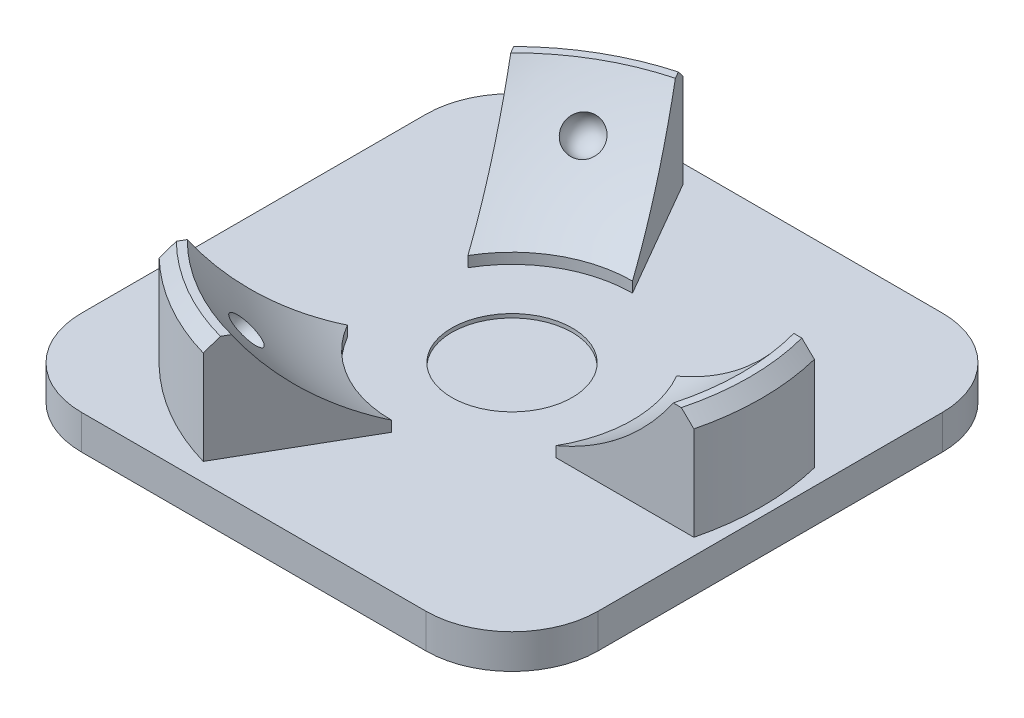
SolidWorks part; units mm, degrees
ref_plane "Спереди" through (0, 0, 0) normal (0, 0, 1) x (1, 0, 0)
ref_plane "Сверху" through (0, 0, 0) normal (0, 1, 0) x (1, 0, 0)
ref_plane "Справа" through (0, 0, 0) normal (1, 0, 0) x (0, 0, -1)
other "Configuration Table"
sketch "Эскиз1" plane through (0, 0, 0) normal (0, 0, 1) x (1, 0, 0)
  line L0 (11.1355, 0) -> (28.9914, 0)
  line L1 (28.9914, 0) -> (28.9914, 10.9081)
  line L2 (28.9914, 10.9081) -> (27.5772, 12.3223)
  line L3 (27.5772, 12.3223) -> (26.674, 12.3223)
  line L5 (0, 30) -> (44.5124, -14.5124) construction
  line L6 (17.6777, 2.4228) -> (27.5772, 12.3223) construction
  line L7 (0, 0) -> (0, 20.2249) construction
  circle A0 centre (0, 30) radius 30 construction
  circle A2 centre (22.6274, 7.3726) radius 2 construction
  circle A3 centre (0, 30) radius 32 construction
  arc A4 (26.674, 12.3223) -> (11.1355, 0) centre (0, 30) cw
  point P15 (22.6274, 7.3726)
  dimension "D1" = 60
  dimension "D2" = 4
  dimension "D7" = 64
  dimension "D3" = 14
  dimension "D4" = 135
  dimension "D5" = 2
  dimension "D6" = 45
revolve "Повернуть1" add sketch "Эскиз1" angle 360 about L7
sketch "Эскиз2" plane through (0, 0, 0) normal (0, -1, 0) x (1, 0, 0)
  line L0 (-37.3718, 0) -> (42.3587, 0) construction
  line L1 (-37.3718, -7) -> (42.3587, -7) construction
  line L2 (-37.3718, 7) -> (42.3587, 7) construction
  line L3 (4.0414, 7) -> (4.0414, -7)
  line L4 (4.0414, -7) -> (34.1437, -7)
  line L9 (28.1336, 7) -> (4.0414, 7)
  line L18 (34.1437, 7) -> (28.1336, 7)
  circle A0 centre (0, 0) radius 28.9914 construction
  arc A2 (34.1437, 7) -> (34.1437, -7) centre (0, 0) ccw
  point P22 (0, 0)
  dimension "D1" = 7
  dimension "D2" = 7
extrude "Вырез-Вытянуть1" cut sketch "Эскиз2" against normal through all
ref_axis "Ось1" through (0, 0, 0) along (0, 1, 0)
sketch "Эскиз3" plane through (0, 0, 0) normal (0, 0, 1) x (1, 0, 0)
  line L0 (0, 30) -> (43.0518, -13.0518) construction
  line L1 (0, 0) -> (0, 30) construction
  line L2 (21.2132, 8.7868) -> (24.0416, 5.9584)
  circle A0 centre (0, 30) radius 30 construction
  circle A1 centre (22.6274, 7.3726) radius 2 construction
  arc A2 (24.0416, 5.9584) -> (21.2132, 8.7868) centre (22.6274, 7.3726) cw
  dimension "D1" = 60
  dimension "D2" = 4
  dimension "D3" = 30
  dimension "D4" = 45
revolve "Вырез-Повернуть3" cut sketch "Эскиз3" angle 360 about L0
pattern_circular "Круговой массив5" count 3 over 360 about axis through (0, 0, 0) along (0, 1, 0) of "Повернуть1"
sketch "Эскиз4" plane through (0, 0, 0) normal (0, -1, 0) x (1, 0, 0)
  line L1 (-20, -30) -> (20, -30)
  line L2 (-30, -20) -> (-30, 20)
  line L3 (-20, 30) -> (20, 30)
  line L4 (30, -20) -> (30, 20)
  line L5 (-30, -30) -> (30, 30) construction
  line L6 (-30, 30) -> (30, -30) construction
  arc A0 (-30, 20) -> (-20, 30) centre (-20, 20) cw
  arc A1 (-20, -30) -> (-30, -20) centre (-20, -20) cw
  arc A2 (20, -30) -> (30, -20) centre (20, -20) ccw
  arc A3 (20, 30) -> (30, 20) centre (20, 20) cw
  point P0 (0, 0)
  dimension "D3" = 10
  dimension "D1" = 60
  dimension "D2" = 60
extrude "Бобышка-Вытянуть1" add sketch "Эскиз4" along normal blind 4
sketch "Эскиз5" plane through (0, 0, 0) normal (0, 1, 0) x (1, 0, 0)
  circle A0 centre (0, 0) radius 14
  dimension "D1" = 28
extrude "Вырез-Вытянуть2" cut sketch "Эскиз5" along normal through all
sketch "Эскиз6" plane through (0, 0, 0) normal (0, 1, 0) x (1, 0, 0)
  circle A0 centre (0, 0) radius 7
  dimension "D1" = 14
extrude "Вырез-Вытянуть3" cut sketch "Эскиз6" against normal through all
sketch "Эскиз7" plane through (0, -4, 0) normal (0, -1, 0) x (1, 0, 0)
  line L1 (-14.1, -8.1) -> (16.1, -8.1)
  line L2 (-14.1, -8.1) -> (-14.1, 8.1)
  line L3 (-14.1, 8.1) -> (16.1, 8.1)
  line L4 (16.1, -8.1) -> (16.1, 8.1)
  line L5 (-14.1, -8.1) -> (16.1, 8.1) construction
  line L6 (-14.1, 8.1) -> (16.1, -8.1) construction
  point P0 (1, 0)
  point P5 (-2.8114, 0)
  point P7 (3.1573, 0)
  point P8 (16.1, 0)
  dimension "D1" = 16.2
  dimension "D2" = 30.2
  dimension "D3" = 16.1
extrude "Вырез-Вытянуть4" cut sketch "Эскиз7" against normal blind 3.35
sketch "Эскиз8" plane through (0, -0.65, 0) normal (0, -1, 0) x (1, 0, 0)
  circle A0 centre (0, 0) radius 7 construction
  circle A1 centre (0, 0) radius 7
extrude "Бобышка-Вытянуть2" add sketch "Эскиз8" against normal blind 0.2
